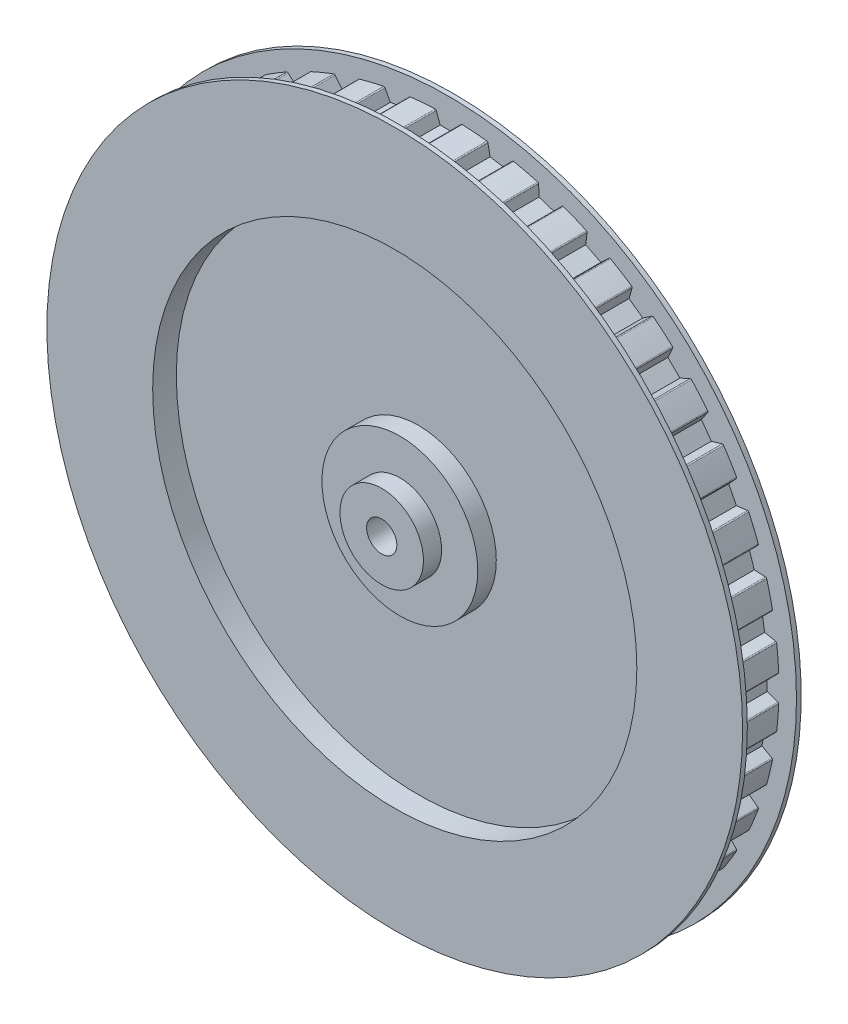
SolidWorks part; units mm, degrees
material "Nylon 101"
ref_plane "Front Plane" through (0, 0, 0) normal (0, 0, 1) x (1, 0, 0)
ref_plane "Top Plane" through (0, 0, 0) normal (0, 1, 0) x (1, 0, 0)
ref_plane "Right Plane" through (0, 0, 0) normal (1, 0, 0) x (0, 0, -1)
sketch "Sketch1" plane through (0, 0, 0) normal (0, 1, 0) x (1, 0, 0)
  line L0 (63.5, -10.3187) -> (0, -10.3187)
  line L1 (0, -10.3187) -> (0, -12.3031)
  line L2 (0, -12.3031) -> (63.5, -12.3031)
  line L3 (63.5, -12.3031) -> (63.5, -10.3187)
  line L4 (0, -10.3187) -> (0, -12.3031) construction
  dimension "D1" = 63.5
  dimension "D2" = 1.9844
revolve "Revolve1" add sketch "Sketch1" angle 360 about L4 reverse direction yes
sketch "Sketch2" plane through (0, 0, 10.3187) normal (0, 0, -1) x (-1, 0, 0)
  line L0 (20.8148, -56.5864) -> (19.4459, -54.8343)
  line L1 (19.4459, -54.8343) -> (16.4988, -55.7919)
  line L2 (16.4988, -55.7919) -> (16.4212, -58.014)
  line L3 (-25.2944, -54.7309) -> (-25.0234, -52.524)
  line L4 (-25.0234, -52.524) -> (-27.7845, -51.1172)
  line L5 (-27.7845, -51.1172) -> (-29.4106, -52.6336)
  line L6 (-52.6336, -29.4106) -> (-51.1172, -27.7845)
  line L7 (-51.1172, -27.7845) -> (-52.524, -25.0234)
  line L8 (-52.524, -25.0234) -> (-54.7309, -25.2944)
  line L9 (-58.014, 16.4212) -> (-55.7919, 16.4988)
  line L10 (-55.7919, 16.4988) -> (-54.8343, 19.4459)
  line L11 (-54.8343, 19.4459) -> (-56.5864, 20.8148)
  line L12 (-37.2822, 47.3848) -> (-35.4389, 46.1414)
  line L13 (-35.4389, 46.1414) -> (-32.9319, 47.9629)
  line L14 (-32.9319, 47.9629) -> (-33.5448, 50.1002)
  line L15 (7.1436, 59.8686) -> (7.5678, 57.686)
  line L16 (7.5678, 57.686) -> (10.6285, 57.2012)
  line L17 (10.6285, 57.2012) -> (11.7064, 59.1459)
  line L18 (40.9692, 44.2358) -> (40.0295, 42.2207)
  line L19 (40.0295, 42.2207) -> (42.2207, 40.0295)
  line L20 (42.2207, 40.0295) -> (44.2358, 40.9692)
  line L21 (59.1459, 11.7064) -> (57.2012, 10.6285)
  line L22 (57.2012, 10.6285) -> (57.686, 7.5678)
  line L23 (57.686, 7.5678) -> (59.8686, 7.1436)
  line L24 (50.1002, -33.5448) -> (47.9629, -32.9319)
  line L25 (47.9629, -32.9319) -> (46.1414, -35.4389)
  line L26 (46.1414, -35.4389) -> (47.3848, -37.2822)
  arc A0 (47.3848, -37.2822) -> (20.8148, -56.5864) centre (0, 0) cw
  arc A1 (16.4212, -58.014) -> (-25.2944, -54.7309) centre (0, 0) cw
  arc A2 (-29.4106, -52.6336) -> (-52.6336, -29.4106) centre (0, 0) cw
  arc A3 (-54.7309, -25.2944) -> (-58.014, 16.4212) centre (0, 0) cw
  arc A4 (-56.5864, 20.8148) -> (-37.2822, 47.3848) centre (0, 0) cw
  arc A5 (-33.5448, 50.1002) -> (7.1436, 59.8686) centre (0, 0) cw
  arc A6 (11.7064, 59.1459) -> (40.9692, 44.2358) centre (0, 0) cw
  arc A7 (44.2358, 40.9692) -> (59.1459, 11.7064) centre (0, 0) cw
  arc A8 (59.8686, 7.1436) -> (50.1002, -33.5448) centre (0, 0) cw
  circle A9 centre (0, 0) radius 63.5 construction
  dimension "D1" = 60.2933
  dimension "D2" = 60.2933
  dimension "D3" = 60.2933
  dimension "D4" = 60.2932
  dimension "D5" = 60.2933
  dimension "D6" = 60.2933
  dimension "D7" = 60.2932
  dimension "D8" = 60.2933
  dimension "D9" = 60.2933
  dimension "D10" = 7.1436
  dimension "D11" = 7.5678
  dimension "D12" = 10.6285
  dimension "D13" = 11.7064
  dimension "D14" = 16.4212
  dimension "D15" = 16.4988
  dimension "D16" = 19.4459
  dimension "D17" = 20.8148
  dimension "D18" = 40.0295
  dimension "D19" = 40.9692
  dimension "D20" = 42.2207
  dimension "D21" = 44.2358
  dimension "D22" = 46.1414
  dimension "D23" = 47.3848
  dimension "D24" = 47.9629
  dimension "D25" = 50.1002
  dimension "D26" = 57.2012
  dimension "D27" = 57.686
  dimension "D28" = 59.1459
  dimension "D29" = 59.8686
  dimension "D30" = 25.0234
  dimension "D31" = 25.2944
  dimension "D32" = 27.7845
  dimension "D33" = 29.4106
  dimension "D34" = 32.9319
  dimension "D35" = 33.5448
  dimension "D36" = 35.4389
  dimension "D37" = 37.2822
  dimension "D38" = 51.1172
  dimension "D39" = 52.524
  dimension "D40" = 52.6336
  dimension "D41" = 54.7309
  dimension "D42" = 54.8343
  dimension "D43" = 55.7919
  dimension "D44" = 56.5864
  dimension "D45" = 58.014
  dimension "D46" = 7.1436
  dimension "D47" = 7.5678
  dimension "D48" = 10.6285
  dimension "D49" = 11.7064
  dimension "D51" = 16.4988
  dimension "D52" = 19.4459
  dimension "D54" = 40.0295
  dimension "D56" = 42.2207
  dimension "D58" = 46.1414
  dimension "D60" = 47.9629
  dimension "D62" = 57.2012
  dimension "D63" = 57.686
  dimension "D66" = 25.0234
  dimension "D68" = 27.7845
  dimension "D70" = 32.9319
  dimension "D72" = 35.4389
  dimension "D74" = 51.1172
  dimension "D75" = 52.524
  dimension "D78" = 54.8343
  dimension "D79" = 55.7919
extrude "Boss-Extrude1" add sketch "Sketch2" along normal blind 20.6375
ref_plane "Plane1" through (0, 0, -10.3187) normal (0, 0, 1) x (1, 0, 0)
sketch "Sketch3" plane through (0, 0, -10.3187) normal (0, 0, 1) x (1, 0, 0)
  circle A0 centre (0, 0) radius 63.5
  dimension "D1" = 127
extrude "Boss-Extrude2" add sketch "Sketch3" against normal blind 1.9844
hole_wizard "Hole1" positions "Sketch5" profile "Sketch4" legacy
sketch "Sketch5" plane through (0, 0, -12.3031) normal (0, 0, -1) x (-1, 0, 0)
  point P0 (0, 0)
sketch "Sketch4" plane through (0, 0, -12.3031) normal (1, 0, 0) x (0, 1, 0)
  line L0 (0, 0) -> (0, 9.9219)
  line L1 (0, 9.9219) -> (44.1912, 9.9219)
  line L2 (44.1912, 9.9219) -> (44.1912, 0)
  line L3 (44.1912, 0) -> (0, 0)
  line L4 (0, 110) -> (0, -10) construction
  dimension "Diameter" = 88.3825
  dimension "Depth" = 9.9219
hole_wizard "Hole2" positions "Sketch7" profile "Sketch6" legacy
sketch "Sketch7" plane through (0, 0, 12.3031) normal (0, 0, 1) x (1, 0, 0)
  point P0 (0, 0)
sketch "Sketch6" plane through (0, 0, 12.3031) normal (1, 0, 0) x (0, -1, 0)
  line L0 (0, 0) -> (0, 9.9219)
  line L1 (0, 9.9219) -> (44.1912, 9.9219)
  line L2 (44.1912, 9.9219) -> (44.1912, 0)
  line L3 (44.1912, 0) -> (0, 0)
  line L4 (0, 110) -> (0, -10) construction
  dimension "Diameter" = 88.3825
  dimension "Depth" = 9.9219
sketch "Sketch8" plane through (0, 0, 0) normal (0, 1, 0) x (1, 0, 0)
  line L0 (14.2875, 12.3031) -> (0, 12.3031)
  line L1 (0, 12.3031) -> (0, 2.3813)
  line L2 (0, 2.3813) -> (14.2875, 2.3813)
  line L3 (14.2875, 2.3813) -> (14.2875, 12.3031)
  line L4 (0, 12.3031) -> (0, 2.3813) construction
  dimension "D1" = 14.2875
  dimension "D2" = 9.9219
revolve "Revolve2" add sketch "Sketch8" angle 360 about L4 reverse direction yes
sketch "Sketch9" plane through (0, 0, 0) normal (0, 1, 0) x (1, 0, 0)
  line L0 (14.224, 0) -> (0, 0)
  line L1 (0, 0) -> (0, -17.78)
  line L2 (0, -17.78) -> (7.62, -17.78)
  line L3 (7.62, -17.78) -> (7.62, -10.16)
  line L4 (7.62, -10.16) -> (14.224, -10.16)
  line L5 (14.224, -10.16) -> (14.224, 0)
  line L6 (0, 0) -> (0, -17.78) construction
  point P7 (0, 0)
  dimension "D1" = 7.62
  dimension "D2" = 14.224
  dimension "D3" = 7.62
  dimension "D4" = 17.78
revolve "Revolve3" add sketch "Sketch9" angle 360 about L6 reverse direction yes
fillet "Fillet1" radius 0.2286 18 edges at (-7.1436, 59.8686, 0) (58.014, 16.4212, 0) (52.6336, -29.4106, 0) (-59.1459, 11.7064, 0) (37.2822, 47.3848, 0) (-59.8686, 7.1436, 0) (-44.2358, 40.9692, 0) (-50.1002, -33.5448, 0) (54.7309, -25.2944, 0) (-47.3848, -37.2822, 0) (56.5864, 20.8148, 0) (-20.8148, -56.5864, 0) (33.5448, 50.1002, 0) (-16.4212, -58.014, 0) (-11.7064, 59.1459, 0) (25.2944, -54.7309, 0) (-40.9692, 44.2358, 0) (29.4106, -52.6336, 0) tangent propagation no
sketch "Sketch12" plane through (0, 0, -10.3187) normal (0, 0, 1) x (1, 0, 0)
  line L0 (35.4389, 46.1414) -> (37.1438, 47.2914) construction
  line L1 (32.9319, 47.9629) -> (35.4389, 46.1414) construction
  line L2 (33.4987, 49.9397) -> (32.9319, 47.9629) construction
  line L3 (35.4389, 46.1414) -> (37.1438, 47.2914)
  line L4 (32.9319, 47.9629) -> (35.4389, 46.1414)
  line L5 (33.4987, 49.9397) -> (32.9319, 47.9629)
  arc A0 (37.4135, 47.2812) -> (37.1438, 47.2914) centre (37.2716, 47.1019) ccw construction
  arc A1 (33.4987, 49.9397) -> (33.4057, 50.193) centre (33.279, 50.0027) ccw construction
  arc A2 (37.4135, 47.2812) -> (37.1438, 47.2914) centre (37.2716, 47.1019) ccw
  arc A3 (33.4987, 49.9397) -> (33.4057, 50.193) centre (33.279, 50.0027) ccw
  arc A4 (33.4057, 50.193) -> (37.4135, 47.2812) centre (0.056, 0.0771) cw
  dimension "D1" = 60.198
extrude "Cut-Extrude1" cut sketch "Sketch12" along normal blind 20.6502
pattern_circular "CirPattern2" count 40 over 360 about axis through (0, 0, 12.3031) along (0, 0, 1) of "Cut-Extrude1"
scale "Scale1" bodies to scale 112 scale about origin uniform scaling no x scale factor 2.3 y scale factor 2.3 z scale factor 1
sketch "Sketch13" plane through (0, 0, 0) normal (0, 0, 1) x (1, 0, 0)
  circle A0 centre (0, 0) radius 6.35
  dimension "D1" = 12.7
extrude "Cut-Extrude2" cut sketch "Sketch13" against normal through all both and the other way through all
equation "\"0.8125in.\"=0.813"
equation "\"D1@Cut-Extrude1\"=\"0.8125in.\""
